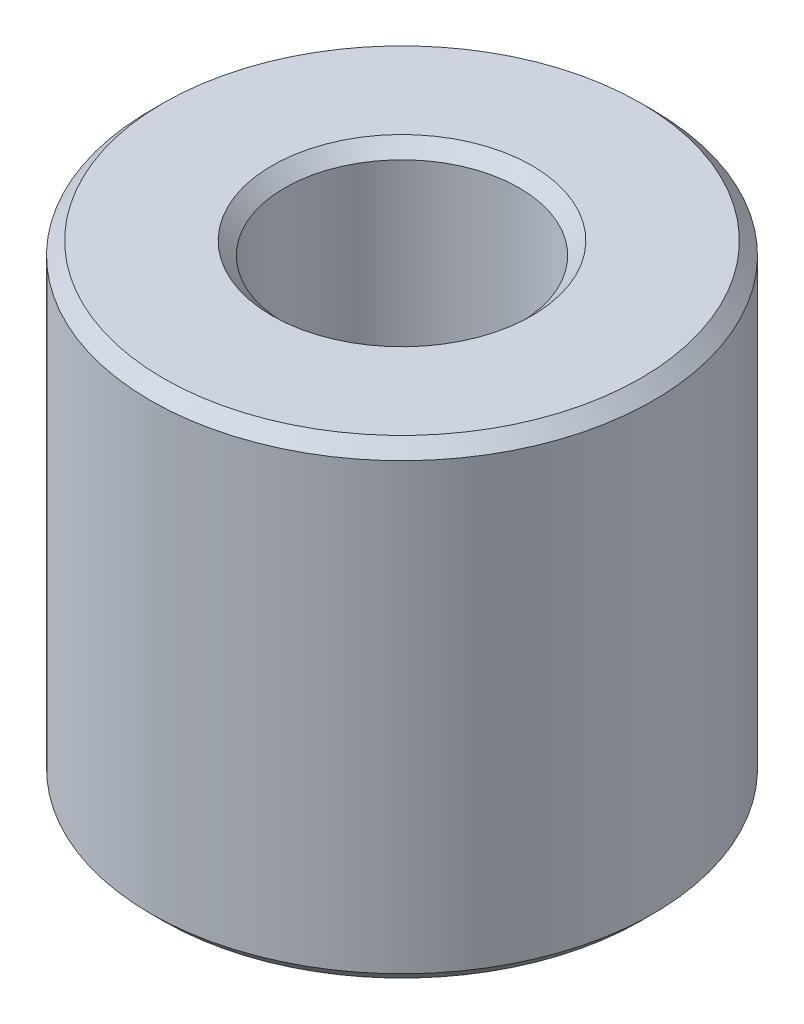
SolidWorks part; units mm, degrees
ref_plane "Front Plane" through (0, 0, 0) normal (0, 0, 1) x (1, 0, 0)
ref_plane "Top Plane" through (0, 0, 0) normal (0, 1, 0) x (1, 0, 0)
ref_plane "Right Plane" through (0, 0, 0) normal (1, 0, 0) x (0, 0, -1)
sketch "Sketch1" plane through (0, 0, 0) normal (0, 1, 0) x (1, 0, 0)
  circle A0 centre (0, 0) radius 55
  dimension "SLEEVE_OD" = 110
extrude "Boss-Extrude1" add sketch "Sketch1" along normal blind 102.8238
sketch "Sketch2" plane through (0, 0, 0) normal (0, 1, 0) x (1, 0, 0)
  circle A0 centre (0, 0) radius 25.6386
  dimension "BORE_D" = 51.2772
extrude "Cut-Extrude1" cut sketch "Sketch2" along normal through all
chamfer "Chamfer1" distance 2.8049 angle 45 4 edges at (0, 102.8238, 25.6386) (0, 0, 25.6386) (0, 0, 55) (0, 102.8238, 55)
